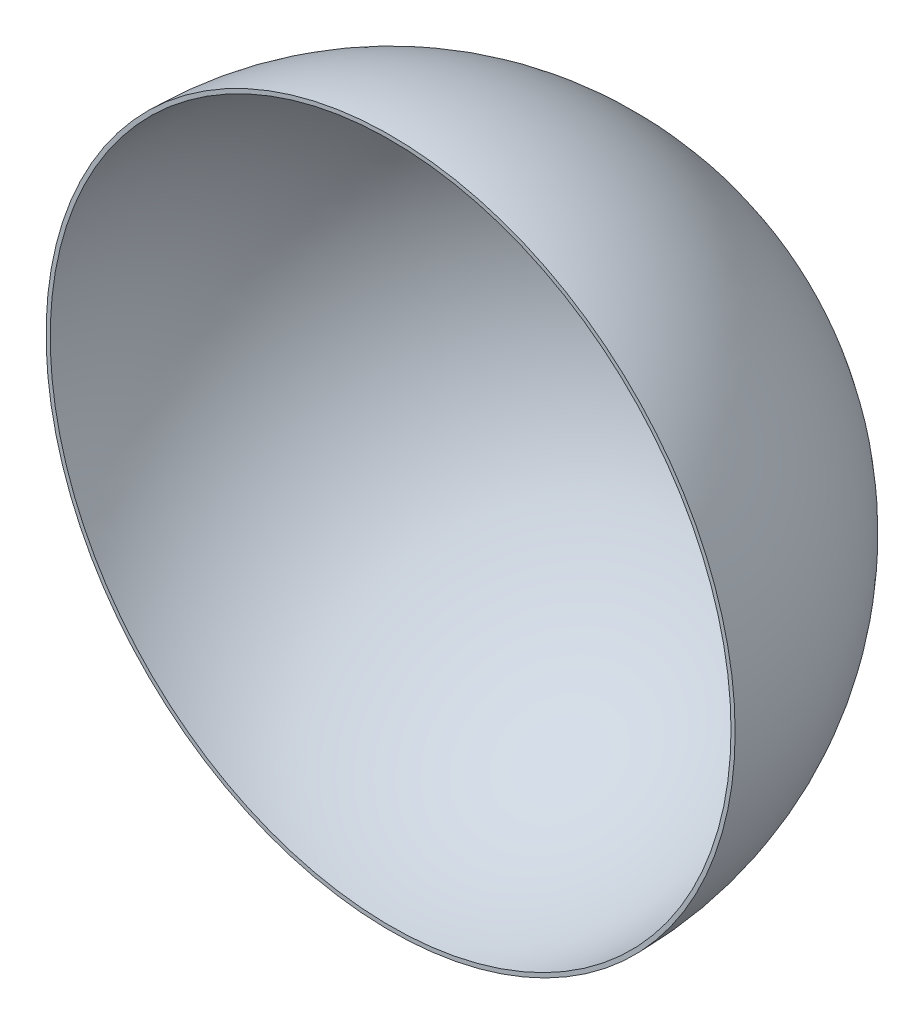
SolidWorks part; units mm, degrees
ref_plane "Ebene vorne" through (0, 0, 0) normal (0, 0, 1) x (1, 0, 0)
ref_plane "Ebene oben" through (0, 0, 0) normal (0, 1, 0) x (1, 0, 0)
ref_plane "Ebene rechts" through (0, 0, 0) normal (1, 0, 0) x (0, 0, -1)
sketch "Skizze1" plane through (0, 0, 0) normal (0, 0, 1) x (1, 0, 0)
  line L0 (-250, 0) -> (250, 0) construction
  arc A0 (-250, 0) -> (250, 0) centre (0, 0) ccw
  point P4 (-250, 0)
  dimension "D1" = 250
ref_axis "Achse1" through (-250, 0, 0) along (1, 0, 0)
revolve "Rotation-Dünn1" add sketch "Skizze1" angle 180 about axis through (-250, 0, 0) along (1, 0, 0) wall 3
ref_plane "Ebene2" through (0, 0, 0) normal (0, 0, 1) x (1, 0, 0)
ref_axis "Achse2" through (0, 0, 0) along (0, 0, 1)
